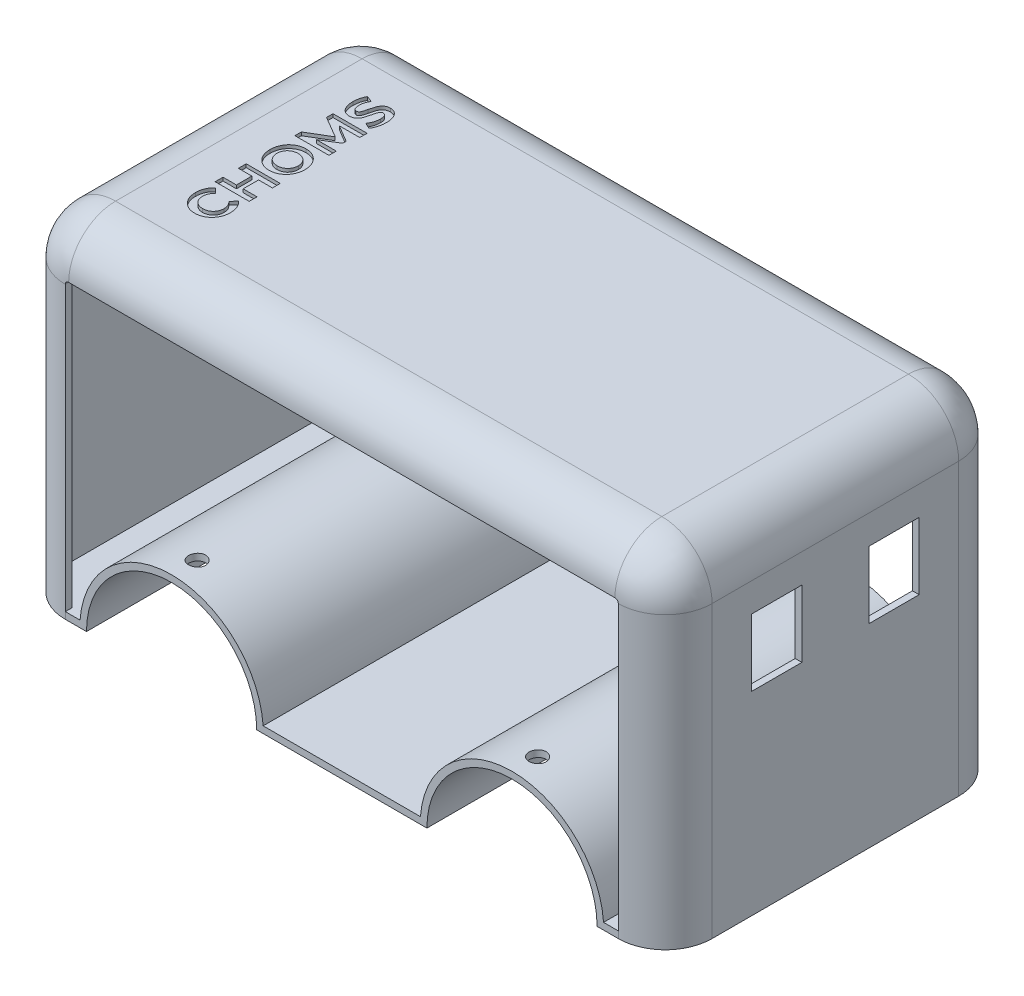
SolidWorks part; units mm, degrees
ref_plane "Front Plane" through (0, 0, 0) normal (0, 0, 1) x (1, 0, 0)
ref_plane "Top Plane" through (0, 0, 0) normal (0, 1, 0) x (1, 0, 0)
ref_plane "Right Plane" through (0, 0, 0) normal (1, 0, 0) x (0, 0, -1)
sketch "Sketch1" plane through (0, 0, 0) normal (0, 0, 1) x (1, 0, 0)
  line L0 (-127, 0) -> (127, 0)
  line L1 (-407.6, 508) -> (407.6, 508)
  line L2 (-482.6, 433) -> (-482.6, 0)
  line L3 (-482.6, 0) -> (-381, 0)
  line L4 (482.6, 433) -> (482.6, 0)
  line L5 (381, 0) -> (482.6, 0)
  arc A0 (-407.6, 508) -> (-482.6, 433) centre (-407.6, 433) ccw
  arc A1 (482.6, 433) -> (407.6, 508) centre (407.6, 433) ccw
  arc A2 (-127, 0) -> (-381, 0) centre (-254, 0) ccw
  arc A3 (381, 0) -> (127, 0) centre (254, 0) ccw
  dimension "D5" = 150
  dimension "D6" = 150
  dimension "D7" = 254
  dimension "D8" = 254
  dimension "D1" = 965.2
  dimension "D2" = 508
  dimension "D3" = 482.6
  dimension "D4" = 508
  dimension "D9" = 508
  dimension "D10" = 254
extrude "Boss-Extrude1" add sketch "Sketch1" along normal mid plane 508
fillet "Fillet1" radius 70 10 edges at (482.6, 216.5, 254) (460.633, 486.033, 254) (-482.6, 216.5, 254) (-460.633, 486.033, 254) (482.6, 216.5, -254) (460.633, 486.033, -254) (-482.6, 216.5, -254) (-460.633, 486.033, -254) (0, 508, 254) (0, 508, -254)
shell "Shell3" thickness 10 removed face at (0, 199.8071, 254) removed face at (0, 199.8071, -254)
ref_plane "Plane1" through (0, -101.6, 0) normal (0, -1, 0) x (-1, 0, 0)
ref_plane "Plane2" through (0, 0, 0) normal (0, -1, 0) x (-1, 0, 0)
ref_plane "Plane3" through (0, 140, 0) normal (0, -1, 0) x (-1, 0, 0)
sketch "Sketch2" plane through (0, 140, 0) normal (0, -1, 0) x (-1, 0, 0)
  line L0 (-127, 254) -> (-381, 254) construction
  line L1 (381, 254) -> (127, 254) construction
  line L2 (127, -254) -> (381, -254) construction
  line L3 (-381, -254) -> (-127, -254) construction
  circle A0 centre (-254, 215.9) radius 12.7
  circle A1 centre (254, 215.9) radius 12.7
  circle A2 centre (254, -215.9) radius 12.7
  circle A3 centre (-254, -215.9) radius 12.7
  point P17 (0, 0)
  point P18 (0, 0)
  dimension "D1" = 25.4
  dimension "D2" = 25.4
  dimension "D3" = 25.4
  dimension "D4" = 25.4
  dimension "D5" = 254
  dimension "D6" = 38.1
  dimension "D7" = 38.1
  dimension "D8" = 254
  dimension "D9" = 38.1
  dimension "D10" = 38.1
  dimension "D11" = 254
  dimension "D12" = 254
extrude "Cut-Extrude1" cut sketch "Sketch2" along normal blind 107 contours A3 | A0 | A1 | A2
sketch "Sketch3" plane through (482.6, 0, 0) normal (1, 0, 0) x (0, 0, -1)
  line L1 (-125, 390) -> (-50, 390)
  line L2 (-125, 390) -> (-125, 290)
  line L3 (-125, 290) -> (-50, 290)
  line L4 (-50, 390) -> (-50, 290)
  line L5 (50, 390) -> (125, 390)
  line L6 (50, 390) -> (50, 290)
  line L7 (50, 290) -> (125, 290)
  line L8 (125, 390) -> (125, 290)
  line L9 (-384.9663, 0) -> (384.9663, 0) construction
  line L10 (-184, 0) -> (184, 0) construction
  point P12 (0, 0)
  dimension "D1" = 100
  dimension "D2" = 75
  dimension "D3" = 75
  dimension "D4" = 100
  dimension "D5" = 290
  dimension "D6" = 290
  dimension "D7" = 50
  dimension "D8" = 50
extrude "Cut-Extrude2" cut sketch "Sketch3" against normal blind 10
ref_axis "Axis1" through (-254, 125.6426, 215.9) along (0, 1, 0)
ref_axis "Axis2" through (254, 99.3051, 215.9) along (0, 1, 0)
ref_axis "Axis3" through (254, 72.2514, -215.9) along (0, 1, 0)
ref_axis "Axis4" through (-254, 125.6426, -215.9) along (0, 1, 0)
sketch "Sketch4" plane through (0, 508, 0) normal (0, 1, 0) x (1, 0, 0)
  line L0 (-307.6, 184) -> (-307.6, -184) construction
  line L1 (-407.6, -184) -> (407.6, -184) construction
  line L2 (407.6, 184) -> (-407.6, 184) construction
  line L3 (-407.6, -184) -> (-407.6, 184) construction
  text T0 "CHOMS" font "Montserrat" height 50.8
  point P4 (-309.9214, 184)
  dimension "D1" = 100
extrude "Cut-Extrude3" cut sketch "Sketch4" against normal blind 5
